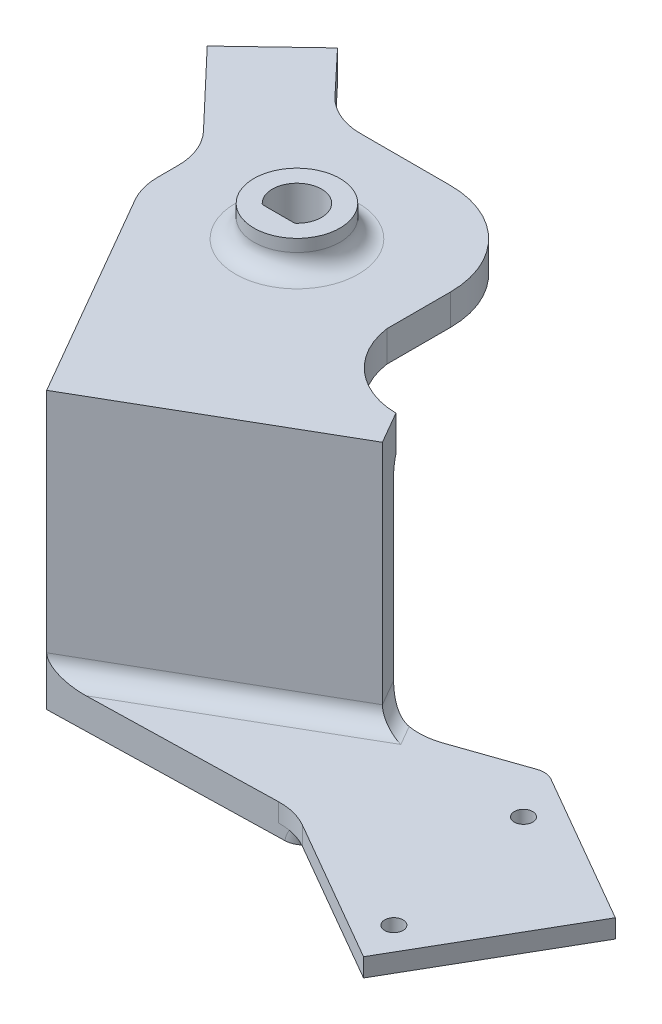
SolidWorks part; units mm, degrees
ref_plane "Front Plane" through (0, 0, 0) normal (0, 0, 1) x (1, 0, 0)
ref_plane "Top Plane" through (0, 0, 0) normal (0, 1, 0) x (1, 0, 0)
ref_plane "Right Plane" through (0, 0, 0) normal (1, 0, 0) x (0, 0, -1)
sketch "Sketch1" plane through (0, 0, 0) normal (0, 1, 0) x (1, 0, 0)
  line L0 (0, -4) -> (0, -3) construction
  line L1 (-20, 20) -> (20, 20) construction
  line L2 (-20, 20) -> (-20, 14) construction
  line L3 (-20, -20) -> (20, -20) construction
  line L4 (20, 20) -> (20, -20) construction
  line L5 (-20, 20) -> (20, -20) construction
  line L6 (-20, -20) -> (20, 20) construction
  line L11 (0, 0) -> (35.9445, -62.2576) construction
  line L12 (-20, -20) -> (20, -20) construction
  line L13 (-2.6458, -3) -> (2.6458, -3)
  line L14 (-20, -20) -> (-20, -22) construction
  line L15 (-20, -22) -> (20, -22) construction
  line L16 (20, -20) -> (20, -22) construction
  line L17 (1, -41.7321) -> (35.641, -21.7321)
  line L18 (35.641, -21.7321) -> (32.641, -16.5359)
  line L19 (1, -41.7321) -> (-20, -5.359)
  line L20 (-20, 20) -> (-20, 14) construction
  line L21 (20, 5) -> (20, -5.359)
  line L22 (-14, 20) -> (-23.5932, 30.1966)
  line L25 (-20, 4.641) -> (-20, -5.359)
  line L26 (-14, 20) -> (5, 20)
  line L30 (-20, 4.641) -> (-20, -20) construction
  line L31 (-20, 4.641) -> (-20, -5.359) construction
  line L32 (-34.4664, 19.8635) -> (-23.5932, 30.1966)
  line L33 (-34.4664, 19.8635) -> (-20, 4.641)
  circle A0 centre (0, 0) radius 4 construction
  arc A3 (-2.6458, -3) -> (2.6458, -3) centre (0, 0) cw
  arc A4 (20, -5.359) -> (32.641, -16.5359) centre (32.8718, -3.5379) ccw
  arc A5 (20, 5) -> (5, 20) centre (5, 5) ccw
  point P0 (0, 0)
  point P19 (0, -3)
  point P25 (18.3205, -31.7321)
  dimension "D3" = 8
  dimension "D6" = 14
  dimension "D7" = 21
  dimension "D8" = 1
  dimension "D4" = 15
  dimension "D5" = 15
  dimension "D9" = 10
  dimension "D11" = 20
  dimension "D12" = 20
  dimension "D22" = 13
  dimension "D1" = 40
  dimension "D2" = 40
  dimension "D13" = 42
  dimension "D14" = 30
  dimension "D15" = 40
  dimension "D16" = 42
  dimension "D17" = 6
  dimension "D18" = 6
  dimension "D21" = 6
extrude "Boss-Extrude1" add sketch "Sketch1" along normal blind 5
sketch "Sketch2" plane through (0, 5, 0) normal (0, 1, 0) x (1, 0, 0)
  line L0 (0, -4) -> (0, -3) construction
  line L1 (-2.6458, -3) -> (2.6458, -3)
  circle A0 centre (0, 0) radius 4 construction
  arc A1 (-2.6458, -3) -> (2.6458, -3) centre (0, 0) cw
  circle A2 centre (0, 0) radius 7
  point P7 (0, -3)
  dimension "D1" = 8
  dimension "D3" = 14
  dimension "D2" = 1
extrude "Boss-Extrude2" add sketch "Sketch2" along normal blind 5
sketch "Sketch7" plane through (0, 0, 0) normal (0, -1, 0) x (1, 0, 0)
  line L0 (1, 41.7321) -> (35.641, 21.7321)
  line L1 (35.641, 21.7321) -> (33.141, 17.4019)
  line L2 (35.641, 21.7321) -> (32.641, 16.5359) construction
  line L3 (33.141, 17.4019) -> (-1.5, 37.4019)
  line L4 (-20, 5.359) -> (1, 41.7321) construction
  line L5 (-1.5, 37.4019) -> (1, 41.7321)
  dimension "D1" = 40
  dimension "D2" = 5
extrude "Boss-Extrude6" add sketch "Sketch7" along normal blind 40
sketch "Sketch8" plane through (0, -40, 0) normal (0, -1, 0) x (1, 0, 0)
  line L0 (0, 0) -> (82.423, 47.587) construction
  line L2 (35.641, 21.7321) -> (32.641, 16.5359) construction
  line L3 (40.641, 40.7846) -> (55.641, 14.8038)
  line L4 (55.641, 14.8038) -> (35.641, 21.7321)
  line L5 (40.641, 40.7846) -> (1, 41.7321)
  line L6 (1, 41.7321) -> (35.641, 21.7321)
  point P9 (48.141, 27.7942)
  dimension "D1" = 30
  dimension "D2" = 20
  dimension "D3" = 30
extrude "Boss-Extrude7" add sketch "Sketch8" against normal blind 5
sketch "Sketch9" plane through (48.141, 0, 27.7942) normal (0.866, 0, 0.5) x (0.5, 0, -0.866)
  line L0 (15, -35) -> (15, -40) construction
  line L2 (-15, -35) -> (-15, -38)
  line L3 (-15, -38) -> (15, -38)
  line L4 (15, -35) -> (15, -38)
  line L6 (-15, -35) -> (-15, -40) construction
  line L7 (-15, -35) -> (15, -35)
  dimension "D1" = 3
extrude "Boss-Extrude8" add sketch "Sketch9" along normal blind 30
fillet "Fillet1" radius 10 1 edges at (40.641, -36.5, 40.7846)
fillet "Fillet5" radius 10 1 edges at (35.641, -37.5, 21.7321)
fillet "Fillet6" radius 3 1 edges at (34.391, -35, 19.567)
fillet "Fillet7" radius 3 1 edges at (19.6195, -35, 30.9821)
fillet "Fillet9" radius 3 1 edges at (15.8205, 0, 27.4019)
fillet "Fillet19" radius 10 2 edges at (-14, 2.5, -20) (-20, 2.5, -4.641)
fillet "Fillet14" radius 0.5 2 edges at (-2.6458, 5, 3) (2.6458, 5, 3)
fillet "Fillet15" radius 3 1 edges at (48.141, -38, 27.7942)
fillet "Fillet16" radius 3 1 edges at (41.9247, -38.5505, 40.7539)
fillet "Fillet17" radius 3 1 edges at (55.641, -37.5, 14.8038)
sketch "Sketch10" plane through (0, -38, 0) normal (0, -1, 0) x (1, 0, 0)
  line L0 (81.6218, 29.8038) -> (58.0905, 16.2181) construction
  line L1 (45.7095, 37.6626) -> (58.0905, 16.2181) construction
  line L3 (66.6218, 55.7846) -> (43.0728, 42.1886) construction
  circle A0 centre (64.6431, 48.8687) radius 1.5
  circle A1 centre (59.9206, 23.0482) radius 1.5
  dimension "D1" = 3
  dimension "D2" = 3
  dimension "D3" = 5
  dimension "D4" = 5
  dimension "D5" = 22
  dimension "D6" = 5
extrude "Cut-Extrude1" cut sketch "Sketch10" against normal blind 10
fillet "Fillet18" radius 10 1 edges at (-20, 2.5, 5.359)
fillet "Fillet20" radius 3 1 edges at (0, 5, 7)
